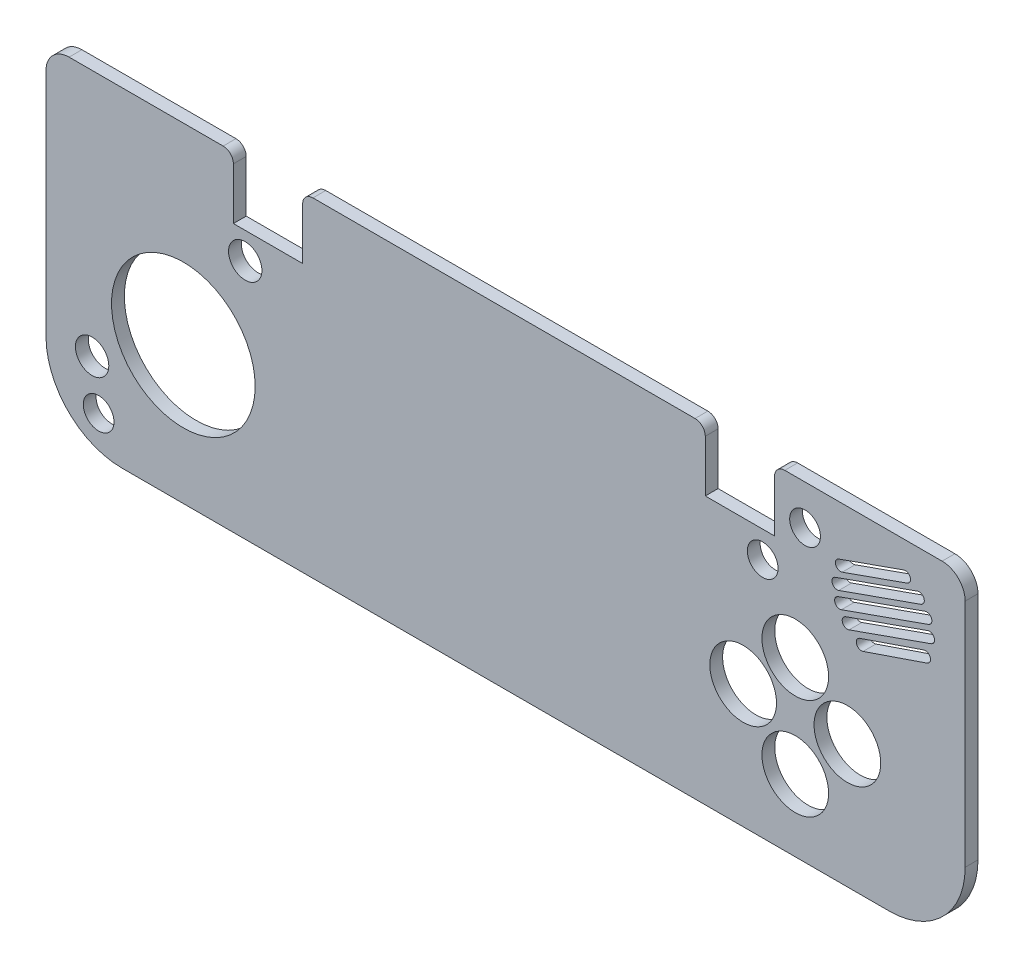
SolidWorks part; units mm, degrees
ref_plane "Plan de face" through (0, 0, 0) normal (0, 0, 1) x (1, 0, 0)
ref_plane "Plan de dessus" through (0, 0, 0) normal (0, 1, 0) x (1, 0, 0)
ref_plane "Plan de droite" through (0, 0, 0) normal (1, 0, 0) x (0, 0, -1)
sketch "Esquisse20" plane through (0, 0, 0) normal (0, 0, 1) x (1, 0, 0)
  line L1 (14.8, -2) -> (164.37, -2)
  line L2 (0, 12.8) -> (0, 57.73)
  line L3 (4.5, 62.23) -> (174.67, 62.23)
  line L4 (179.17, 12.8) -> (179.17, 57.73)
  arc A0 (0, 57.73) -> (4.5, 62.23) centre (4.5, 57.73) cw
  arc A1 (174.67, 62.23) -> (179.17, 57.73) centre (174.67, 57.73) cw
  arc A2 (164.37, -2) -> (179.17, 12.8) centre (164.37, 12.8) ccw
  arc A3 (14.8, -2) -> (0, 12.8) centre (14.8, 12.8) cw
  point P7 (0, 62.23)
  point P10 (179.17, 62.23)
  point P14 (179.17, -2)
  point P17 (0, -2)
extrude "Boss.-Extru.1" add sketch "Esquisse20" along normal blind 2.5
sketch "Esquisse22" plane through (0, 0, 2.5) normal (0, 0, 1) x (1, 0, 0)
  line L0 (14.8, -2) -> (164.37, -2) construction
  line L1 (0, 57.73) -> (0, 12.8) construction
  circle A0 centre (26.77, 24.77) radius 14
  dimension "D1" = 26.77
  dimension "D2" = 26.77
extrude "Enlèv. mat.-Extru.1" cut sketch "Esquisse22" against normal blind 2.5
sketch "Esquisse23" plane through (0, 0, 2.5) normal (0, 0, 1) x (1, 0, 0)
  line L0 (14.8, -2) -> (164.37, -2) construction
  line L1 (0, 57.73) -> (0, 12.8) construction
  circle A0 centre (8.99, 13.97) radius 3.25
  circle A1 centre (-24.9782, 23.5691) radius 3.25
  dimension "D1" = 15.97
  dimension "D2" = 8.99
extrude "Enlèv. mat.-Extru.2" cut sketch "Esquisse23" against normal blind 2.5
sketch "Esquisse24" plane through (0, 0, 2.5) normal (0, 0, 1) x (1, 0, 0)
  line L0 (36.53, 58.87) -> (50.03, 50.15)
  line L1 (36.53, 58.87) -> (50.03, 58.87)
  line L2 (36.53, 58.87) -> (36.53, 50.15)
  line L3 (36.53, 50.15) -> (50.03, 50.15)
  line L4 (50.03, 58.87) -> (50.03, 50.15)
  line L6 (0, 57.73) -> (0, 12.8) construction
  line L7 (174.67, 62.23) -> (4.5, 62.23) construction
  point P4 (43.28, 54.51)
  dimension "D1" = 13.5
  dimension "D2" = 8.72
  dimension "D3" = 43.28
  dimension "D4" = 7.72
extrude "Enlèv. mat.-Extru.3" cut sketch "Esquisse24" against normal blind 2.5 contours L2 L3 L0 | L4 L1 L0 region at (45.53, 55.9633, 2.5) region at (41.03, 53.0567, 2.5)
sketch "Esquisse25" plane through (0, 0, 2.5) normal (0, 0, 1) x (1, 0, 0)
  line L0 (50.03, 58.87) -> (36.53, 58.87)
  line L1 (50.03, 58.87) -> (50.03, 62.2418)
  line L2 (36.53, 58.87) -> (36.53, 62.2418)
  line L3 (50.03, 62.2418) -> (36.53, 62.2418)
extrude "Enlèv. mat.-Extru.4" cut sketch "Esquisse25" against normal blind 2.5
fillet "Congé1" radius 2 2 edges at (50.03, 62.23, 1.25) (36.53, 62.23, 1.25)
sketch "Esquisse26" plane through (0, 0, 2.5) normal (0, 0, 1) x (1, 0, 0)
  line L0 (179.17, 12.8) -> (179.17, 57.73) construction
  line L1 (174.67, 62.23) -> (52.03, 62.23) construction
  circle A1 centre (156.21, 22.13) radius 6.5
  dimension "D2" = 22.96
  dimension "D3" = 40.1
sketch "Esquisse27" plane through (0, 0, 2.5) normal (0, 0, 1) x (1, 0, 0)
  line L0 (179.17, 12.8) -> (179.17, 57.73) construction
  line L1 (174.67, 62.23) -> (52.03, 62.23) construction
  circle A0 centre (146.05, 11.97) radius 6.5
  circle A1 centre (135.89, 22.13) radius 6.5
  circle A2 centre (146.05, 31.65) radius 6.5
  dimension "D1" = 33.12
  dimension "D2" = 43.28
  dimension "D3" = 33.12
  dimension "D4" = 30.58
  dimension "D5" = 40.1
  dimension "D6" = 50.26
extrude "Enlèv. mat.-Extru.5" cut sketch "Esquisse26" against normal blind 2.5
extrude "Enlèv. mat.-Extru.6" cut sketch "Esquisse27" against normal blind 2.5
sketch "Esquisse30" plane through (0, 0, 2.5) normal (0, 0, 1) x (1, 0, 0)
  line L0 (128.51, 58.87) -> (142.01, 50.15)
  line L1 (128.51, 58.87) -> (142.01, 58.87)
  line L2 (128.51, 58.87) -> (128.51, 50.15)
  line L3 (128.51, 50.15) -> (142.01, 50.15)
  line L4 (142.01, 58.87) -> (142.01, 50.15)
  line L5 (142.01, 58.87) -> (128.51, 50.15)
  line L6 (174.67, 62.23) -> (52.03, 62.23) construction
  line L7 (179.17, 12.8) -> (179.17, 57.73) construction
  line L8 (142.01, 58.87) -> (128.51, 58.87)
  line L9 (142.01, 58.87) -> (142.01, 62.2543)
  line L10 (128.51, 58.87) -> (128.51, 62.2543)
  line L11 (142.01, 62.2543) -> (128.51, 62.2543)
  point P4 (135.26, 54.51)
  line M7 (174.67, 62.23) -> (52.03, 62.23)
  dimension "D1" = 13.5
  dimension "D2" = 8.72
  dimension "D3" = 7.72
  dimension "D4" = 43.91
extrude "Enlèv. mat.-Extru.7" cut sketch "Esquisse30" against normal blind 2.5 contours L10 L1 L9 M7 | L5 L1 L0 | L5 L0 L2 | L0 L5 L3 | L4 L5 L0 region at (135.26, 57.4167, 2.5) region at (135.26, 60.55, 2.5) region at (130.76, 54.51, 2.5) region at (139.76, 54.51, 2.5) region at (135.26, 51.6033, 2.5)
fillet "Congé2" radius 2 2 edges at (142.01, 62.23, 1.25) (128.51, 62.23, 1.25)
sketch "Esquisse31" plane through (0, 0, 2.5) normal (0, 0, 1) x (1, 0, 0)
  line L0 (126.51, 62.23) -> (52.03, 62.23) construction
  line L1 (179.17, 12.8) -> (179.17, 57.73) construction
  circle A0 centre (147.96, 54.51) radius 3
  circle A1 centre (139.7, 44.99) radius 3
  dimension "D1" = 7.72
  dimension "D3" = 17.24
  dimension "D2" = 31.21
  dimension "D4" = 39.47
extrude "Enlèv. mat.-Extru.8" cut sketch "Esquisse31" against normal blind 2.5
sketch "Esquisse32" plane through (0, 0, 2.5) normal (0, 0, 1) x (1, 0, 0)
  line L0 (179.17, 12.8) -> (179.17, 57.73) construction
  line L1 (174.67, 62.23) -> (144.01, 62.23) construction
  line L2 (171.6853, 51.16) -> (154.7147, 45.16) construction
  line L3 (172.0186, 50.2172) -> (155.0481, 44.2172)
  line L4 (171.3519, 52.1028) -> (154.3814, 46.1028)
  line L5 (154.2, 48.16) -> (170.2, 53.8169) construction
  line L6 (153.8667, 49.1028) -> (169.8667, 54.7597)
  line L7 (154.5333, 47.2172) -> (170.5333, 52.874)
  line L8 (154.8754, 51.5808) -> (167.5246, 56.0529) construction
  line L9 (154.5421, 52.5236) -> (167.1912, 56.9957)
  line L10 (155.2088, 50.638) -> (167.8579, 55.1101)
  line L11 (156.2, 42.5031) -> (172.2, 48.16) construction
  line L12 (155.8667, 43.446) -> (171.8667, 49.1028)
  line L13 (156.5333, 41.5603) -> (172.5333, 47.2172)
  line L14 (158.9416, 40.2312) -> (171.4222, 44.5) construction
  line L17 (158.6179, 41.1774) -> (171.0986, 45.4462)
  line L18 (159.2652, 39.285) -> (171.7458, 43.5538)
  circle A0 centre (163.2, 48.16) radius 10
  circle A1 centre (163.2, 48.16) radius 9
  arc A2 (172.0186, 50.2172) -> (171.3519, 52.1028) centre (171.6853, 51.16) ccw
  arc A3 (154.3814, 46.1028) -> (155.0481, 44.2172) centre (154.7147, 45.16) ccw
  arc A4 (153.8667, 49.1028) -> (154.5333, 47.2172) centre (154.2, 48.16) ccw
  arc A5 (170.5333, 52.874) -> (169.8667, 54.7597) centre (170.2, 53.8169) ccw
  arc A6 (154.5421, 52.5236) -> (155.2088, 50.638) centre (154.8754, 51.5808) ccw
  arc A7 (167.8579, 55.1101) -> (167.1912, 56.9957) centre (167.5246, 56.0529) ccw
  arc A8 (155.8667, 43.446) -> (156.5333, 41.5603) centre (156.2, 42.5031) ccw
  arc A9 (172.5333, 47.2172) -> (171.8667, 49.1028) centre (172.2, 48.16) ccw
  arc A12 (158.6179, 41.1774) -> (159.2652, 39.285) centre (158.9416, 40.2312) ccw
  arc A13 (171.7458, 43.5538) -> (171.0986, 45.4462) centre (171.4222, 44.5) ccw
  point P9 (163.2, 48.16)
  point P16 (162.2, 50.9884)
  point P23 (161.2, 53.8169)
  point P30 (164.2, 45.3316)
  point P37 (165.1819, 42.3656)
  dimension "D1" = 15.97
  dimension "D3" = 0.589
  dimension "D2" = 14.07
  dimension "D4" = 3
  dimension "D5" = 3
  dimension "D6" = 3
extrude "Enlèv. mat.-Extru.9" cut sketch "Esquisse32" against normal blind 2.5 contours L10 A7 L9 A6 | L7 A5 L6 A4 | L3 A3 L4 A2 | L13 A9 L12 A8 | L18 A13 L17 A12
sketch "Esquisse33" plane through (0, 0, 2.5) normal (0, 0, 1) x (1, 0, 0)
  line L0 (0, 57.73) -> (0, 12.8) construction
  line L1 (34.53, 62.23) -> (4.5, 62.23) construction
  circle A0 centre (38.83, 44.99) radius 3.25
  dimension "D1" = 38.83
  dimension "D2" = 17.24
extrude "Enlèv. mat.-Extru.10" cut sketch "Esquisse33" against normal blind 10
sketch "Esquisse34" plane through (0, 0, 2.5) normal (0, 0, 1) x (1, 0, 0)
  line L0 (14.8, -2) -> (164.37, -2) construction
  line L1 (0, 57.73) -> (0, 12.8) construction
  circle A0 centre (10.26, 4.99) radius 3
  dimension "D1" = 6.99
  dimension "D2" = 10.26
extrude "Enlèv. mat.-Extru.11" cut sketch "Esquisse34" against normal blind 10
